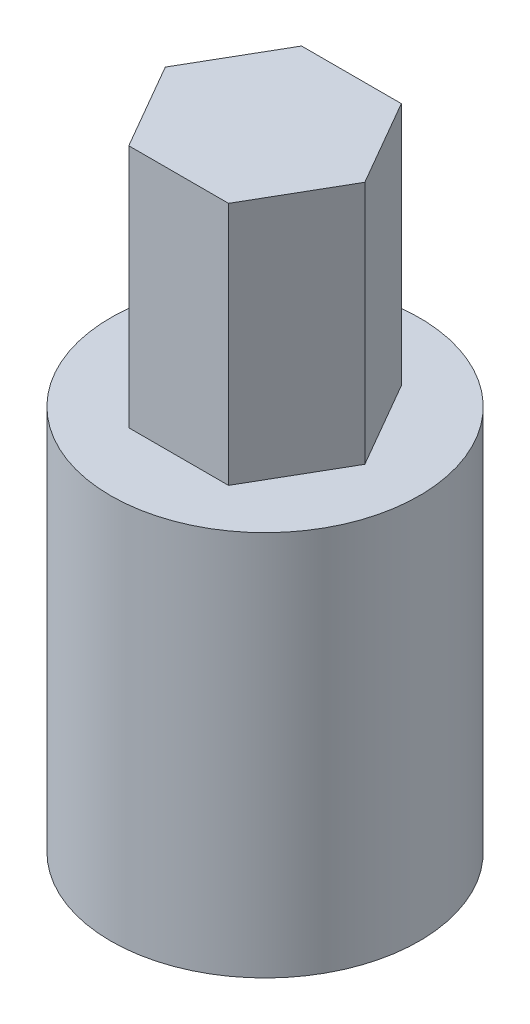
SolidWorks part; units mm, degrees
ref_plane "Front Plane" through (0, 0, 0) normal (0, 0, 1) x (1, 0, 0)
ref_plane "Top Plane" through (0, 0, 0) normal (0, 1, 0) x (1, 0, 0)
ref_plane "Right Plane" through (0, 0, 0) normal (1, 0, 0) x (0, 0, -1)
sketch "Sketch1" plane through (0, 0, 0) normal (0, 1, 0) x (1, 0, 0)
  circle A1 centre (0, 0) radius 6
  dimension "D1" = 12
extrude "Boss-Extrude1" add sketch "Sketch1" along normal blind 15 contours A1 region at (0, 0, 0)
sketch "Sketch4" plane through (0, 15, 0) normal (0, 1, 0) x (1, 0, 0)
  line L1 (1.9399, 3.36) -> (-1.9399, 3.36)
  line L2 (-1.9399, 3.36) -> (-3.8798, 0)
  line L3 (-3.8798, 0) -> (-1.9399, -3.36)
  line L4 (-1.9399, -3.36) -> (1.9399, -3.36)
  line L5 (1.9399, -3.36) -> (3.8798, 0)
  line L6 (3.8798, 0) -> (1.9399, 3.36)
  circle A0 centre (0, 0) radius 3.36 construction
  dimension "D1" = 6.72
extrude "Boss-Extrude2" add sketch "Sketch4" along normal blind 9.5
sketch "Sketch5" plane through (0, 0, 0) normal (0, -1, 0) x (1, 0, 0)
  line L0 (-1.6411, 2.63) -> (1.6411, 2.63)
  circle A0 centre (0, 0) radius 3.1
  dimension "D1" = 6.2
  dimension "D2" = 2.63
extrude "Cut-Extrude1" cut sketch "Sketch5" against normal blind 12 contours L0 A0 region at (0, 0, -0.1011)
